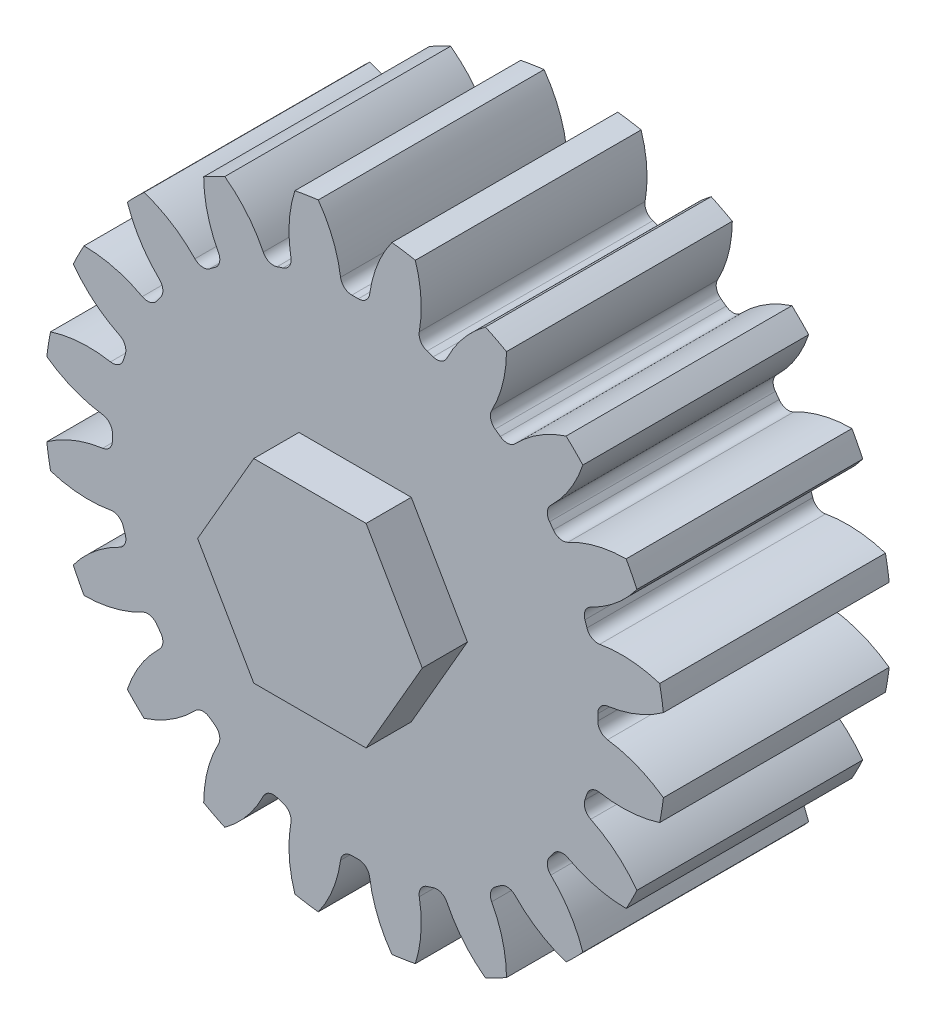
SolidWorks part; units mm, degrees
ref_plane "Front Plane" through (0, 0, 0) normal (0, 0, 1) x (1, 0, 0)
ref_plane "Top Plane" through (0, 0, 0) normal (0, 1, 0) x (1, 0, 0)
ref_plane "Right Plane" through (0, 0, 0) normal (1, 0, 0) x (0, 0, -1)
sketch "Sketch1" plane through (0, 0, 0) normal (0, 0, 1) x (1, 0, 0)
  circle A0 centre (0, 0) radius 31.75
  circle A1 centre (0, 0) radius 34.925
  circle A2 centre (0, 0) radius 27.305
  circle A3 centre (0, 0) radius 2.54
  dimension "D1" = 63.5
  dimension "D2" = 69.85
  dimension "D4" = 5.08
  dimension "D3" = 7.62
extrude "Boss-Extrude2" add sketch "Sketch1" along normal mid plane 25.4 contours A1
sketch "Sketch2" plane through (0, 0, 12.7) normal (0, 0, 1) x (1, 0, 0)
  line L0 (0, 0) -> (0, 37.465) construction
  line L1 (-2.4911, 31.6521) -> (2.4911, 31.6521) construction
  line L2 (-1.526, 27.2623) -> (0, 0) construction
  line L3 (0, 0) -> (5.8608, 37.0037) construction
  line L4 (0, 24.8238) -> (-4.5022, 37.1935) construction
  line L5 (2.4911, 31.6521) -> (7.4119, 30.8727) construction
  arc A0 (-6.1833, 36.9512) -> (-1.526, 27.2623) centre (-15.5683, 26.4763) cw
  arc A1 (6.1833, 36.9512) -> (1.526, 27.2623) centre (15.5683, 26.4763) ccw
  circle A2 centre (0, 0) radius 27.305 construction
  arc A3 (-1.526, 27.2623) -> (1.526, 27.2623) centre (0, 0) cw
  circle A4 centre (0, 0) radius 31.75 construction
  circle A6 centre (0, 0) radius 37.465
  arc A7 (5.8608, 37.0037) -> (-6.1833, 36.9512) centre (0, 0) ccw
  circle M2 centre (0, 0) radius 34.925
  dimension "D2" = 20
  dimension "D3" = 9
extrude "Cut-Extrude3" cut sketch "Sketch2" against normal through all and the other way through all contours A0 A3 A1 M2 region at (0, 31.747, 12.7)
fillet "Fillet1" radius 1.27 1 edges at (-1.526, 27.2623, 0)
fillet "Fillet2" radius 1.27 1 edges at (1.526, 27.2623, 0)
pattern_circular "CirPattern2" count 20 over 360 about axis through (0, 0, 12.7) along (0, 0, -1) of "Fillet2", "Cut-Extrude3", "Fillet1" reverse direction yes
extrude "Cut-Extrude4" cut sketch "Sketch1<4>" against normal through all both and the other way through all contours A3
sketch "Sketch1<4>" plane through (0, 0, 0) normal (0, 0, 1) x (1, 0, 0) same geometry as "Sketch1"
sketch "Sketch3" plane through (0, 0, 12.7) normal (0, 0, 1) x (1, 0, 0)
  line L1 (12.6341, 0) -> (6.317, 10.9414)
  line L2 (6.317, 10.9414) -> (-6.317, 10.9414)
  line L3 (-6.317, 10.9414) -> (-12.6341, 0)
  line L4 (-12.6341, 0) -> (-6.317, -10.9414)
  line L5 (-6.317, -10.9414) -> (6.317, -10.9414)
  line L6 (6.317, -10.9414) -> (12.6341, 0)
  circle A0 centre (0, 0) radius 10.9414 construction
extrude "Boss-Extrude3" add sketch "Sketch3" along normal blind 5.08
equation "\"Module\" = .125in"
equation "\"N\"= 20"
equation "\"D1@Sketch1\"=\"Module\" * \"N\""
equation "\"D2@Sketch1\"=(\"N\" + 2) * \"Module\""
equation "\"D3@Sketch1\"=\"Module\" * if(\"Module\"=> 1.25, 2.25,2.4)"
equation "\"D3@Sketch2\"=180 / \"N\""
equation "\"D1@CirPattern2\"=\"N\""
